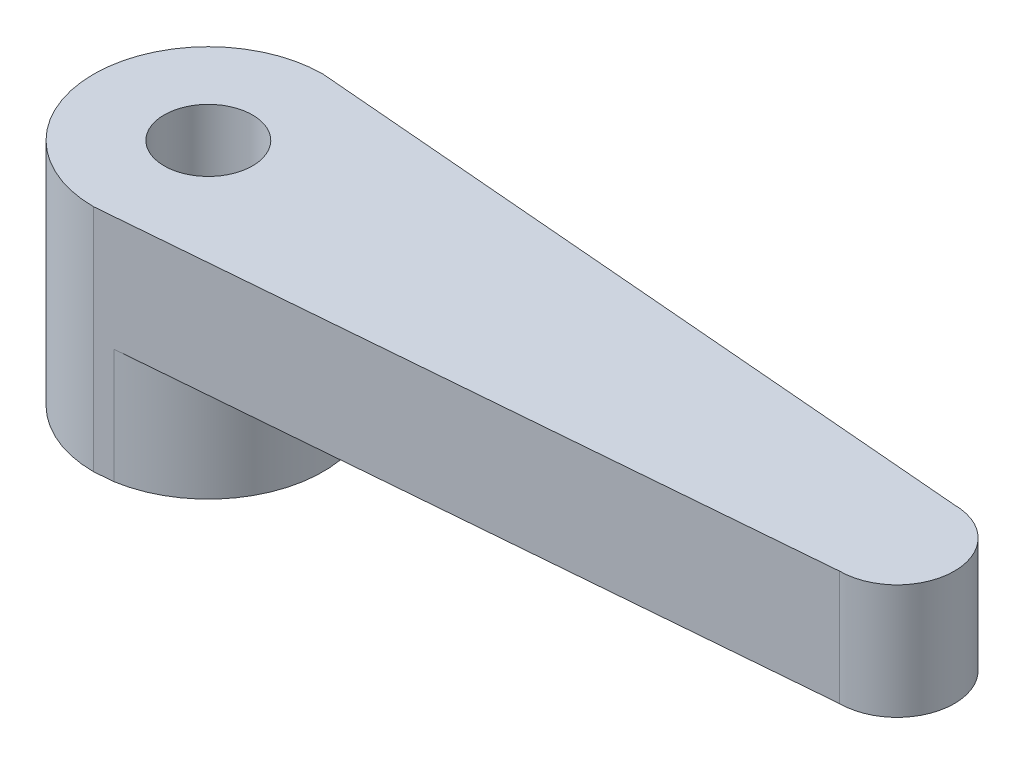
SolidWorks part; units mm, degrees
ref_plane "Front Plane" through (0, 0, 0) normal (0, 0, 1) x (1, 0, 0)
ref_plane "Top Plane" through (0, 0, 0) normal (0, 1, 0) x (1, 0, 0)
ref_plane "Right Plane" through (0, 0, 0) normal (1, 0, 0) x (0, 0, -1)
sketch "Sketch2" plane through (0, 0, 0) normal (0, 1, 0) x (1, 0, 0)
  line L0 (0, 5) -> (30, 2.5)
  line L1 (30, 2.5) -> (30, -2.5) construction
  line L2 (0, -5) -> (30, -2.5)
  circle A0 centre (0, 0) radius 1.925
  arc A1 (0.8276, 4.931) -> (0.8276, -4.931) centre (0, 0) ccw
  arc A2 (30, -2.5) -> (30, 2.5) centre (30, 0) ccw
  circle A3 centre (0, 0) radius 5
  dimension "D1" = 3.85
  dimension "D2" = 10
  dimension "D3" = 30
  dimension "D4" = 5
extrude "Boss-Extrude1" add sketch "Sketch2" along normal blind 5 contours L1 L0 A1 L2 A0 | A2 L1 | L1 L0 A3 L2 region at (0.402, 0, -4.8246) region at (15.7022, 0, 0) region at (31.061, 0, 0)
extrude "Boss-Extrude2" add sketch "Sketch2<3>" against normal blind 5 contours L2 A3 L0 A1 A0 region at (0.402, 0, -4.8246)
sketch "Sketch2<3>" plane through (0, 0, 0) normal (0, 1, 0) x (1, 0, 0) same geometry as "Sketch2"
